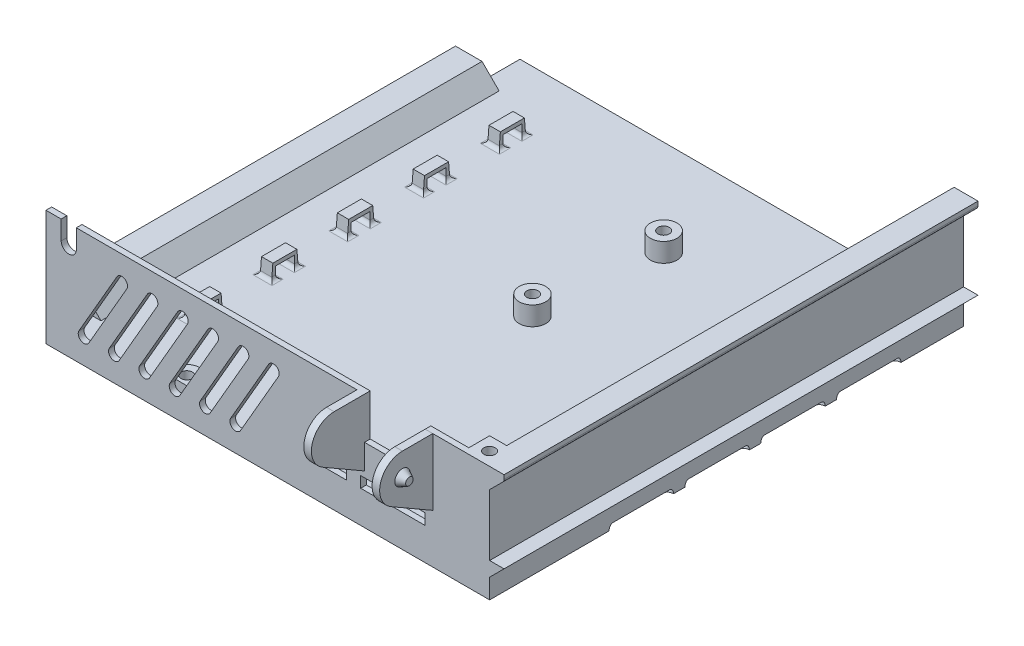
SolidWorks part; units mm, degrees
material "ABS"
ref_plane "Front Plane" through (0, 0, 0) normal (0, 0, 1) x (1, 0, 0)
ref_plane "Top Plane" through (0, 0, 0) normal (0, 1, 0) x (1, 0, 0)
ref_plane "Right Plane" through (0, 0, 0) normal (1, 0, 0) x (0, 0, -1)
ref_axis "Axis1" through (0, 0, 22) along (0, 0, -1)
sketch "Sketch1" plane through (0, 0, 0) normal (0, 1, 0) x (1, 0, 0)
  line L0 (-124, 0) -> (0, 0) construction
  line L1 (124, 0) -> (124, 125) construction
  line L2 (124, 125) -> (-124, 125) construction
  line L3 (-124, 125) -> (-124, 0) construction
  line L4 (40.25, 3.85) -> (40.25, 1.6) construction
  line L5 (38, 101.6) -> (108, 101.6)
  line L6 (38, 101.6) -> (38, 1.6)
  line L7 (38, 1.6) -> (108, 1.6)
  line L8 (108, 101.6) -> (108, 1.6)
  line L9 (38, 101.6) -> (108, 1.6) construction
  line L10 (38, 1.6) -> (108, 101.6) construction
  line L11 (40.25, 3.85) -> (38, 3.85) construction
  line L12 (-113.29, 77.51) -> (-115.54, 77.51) construction
  line L13 (77.2, 11.6) -> (86.2, 11.6)
  line L14 (77.2, 11.6) -> (77.2, 1.6)
  line L15 (77.2, 1.6) -> (86.2, 1.6)
  line L16 (86.2, 11.6) -> (86.2, 1.6)
  line L17 (77.2, 11.6) -> (86.2, 1.6) construction
  line L18 (77.2, 1.6) -> (86.2, 11.6) construction
  line L19 (90, 16.6) -> (107, 16.6)
  line L20 (90, 16.6) -> (90, 1.6)
  line L21 (90, 1.6) -> (107, 1.6)
  line L22 (107, 16.6) -> (107, 1.6)
  line L23 (90, 16.6) -> (107, 1.6) construction
  line L24 (90, 1.6) -> (107, 16.6) construction
  line L25 (-115.54, 113.59) -> (-92.46, 113.59)
  line L26 (-115.54, 113.59) -> (-115.54, 71.41)
  line L27 (-115.54, 71.41) -> (-92.46, 71.41)
  line L28 (-92.46, 113.59) -> (-92.46, 71.41)
  line L29 (-115.54, 113.59) -> (-92.46, 71.41) construction
  line L30 (-115.54, 71.41) -> (-92.46, 113.59) construction
  line L31 (-113.29, 77.51) -> (-113.29, 71.41) construction
  line L32 (-94.71, 107.49) -> (-94.71, 113.59) construction
  line L33 (-94.71, 107.49) -> (-92.46, 107.49) construction
  line L34 (-64.5, 85.45) -> (-68, 85.45) construction
  line L35 (-65, 88.95) -> (-15, 88.95)
  line L36 (-68, 85.95) -> (-68, 6.95)
  line L37 (-65, 3.95) -> (-15, 3.95)
  line L38 (-12, 85.95) -> (-12, 6.95)
  line L39 (-68, 88.95) -> (-12, 3.95) construction
  line L40 (-68, 3.95) -> (-12, 88.95) construction
  line L41 (-64.5, 85.45) -> (-15.5, 85.45) construction
  line L42 (-64.5, 85.45) -> (-64.5, 27.45) construction
  line L43 (-64.5, 27.45) -> (-15.5, 27.45) construction
  line L44 (-15.5, 85.45) -> (-15.5, 27.45) construction
  line L45 (0, 0) -> (0, 125) construction
  line L46 (0, 0) -> (124, 0) construction
  line L47 (-64.5, 85.45) -> (-64.5, 88.95) construction
  line L48 (73, 0.1) -> (73, 125) construction
  line L49 (-65.69, 22.9) -> (-49.81, 22.9)
  line L50 (-65.69, 22.9) -> (-65.69, 1.5)
  line L51 (-65.69, 1.5) -> (-49.81, 1.5)
  line L52 (-49.81, 22.9) -> (-49.81, 1.5)
  line L53 (-65.69, 22.9) -> (-49.81, 1.5) construction
  line L54 (-65.69, 1.5) -> (-49.81, 22.9) construction
  line L55 (-45.65, 19.42) -> (-32.35, 19.42)
  line L56 (-45.65, 19.42) -> (-45.65, 1.5)
  line L57 (-45.65, 1.5) -> (-32.35, 1.5)
  line L58 (-32.35, 19.42) -> (-32.35, 1.5)
  line L59 (-45.65, 19.42) -> (-32.35, 1.5) construction
  line L60 (-45.65, 1.5) -> (-32.35, 19.42) construction
  line L61 (-27.65, 19.42) -> (-14.35, 19.42)
  line L62 (-27.65, 19.42) -> (-27.65, 1.5)
  line L63 (-27.65, 1.5) -> (-14.35, 1.5)
  line L64 (-14.35, 19.42) -> (-14.35, 1.5)
  line L65 (-27.65, 19.42) -> (-14.35, 1.5) construction
  line L66 (-27.65, 1.5) -> (-14.35, 19.42) construction
  line L67 (-40, 0) -> (-40, 125) construction
  line L68 (-113.29, 11.41) -> (-113.29, 17.51) construction
  line L69 (-115.54, 53.59) -> (-92.46, 53.59)
  line L70 (-115.54, 53.59) -> (-115.54, 11.41)
  line L71 (-115.54, 11.41) -> (-92.46, 11.41)
  line L72 (-92.46, 53.59) -> (-92.46, 11.41)
  line L73 (-115.54, 53.59) -> (-92.46, 11.41) construction
  line L74 (-115.54, 11.41) -> (-92.46, 53.59) construction
  line L75 (-113.29, 17.51) -> (-115.54, 17.51) construction
  line L76 (-94.71, 53.59) -> (-94.71, 47.49) construction
  line L77 (-94.71, 47.49) -> (-92.46, 47.49) construction
  line L78 (-104, 0) -> (-104, 32.5) construction
  line L79 (-104, 32.5) -> (-104, 92.5) construction
  line L80 (-104, 92.5) -> (-104, 125) construction
  line L81 (-64.5, 27.45) -> (-15.5, 85.45) construction
  line L82 (-15.5, 27.45) -> (-64.5, 85.45) construction
  circle A0 centre (105, 81.6) radius 1.75
  circle A1 centre (105, 19.6) radius 1.75
  circle A2 centre (70.1, 99.8) radius 1.75
  circle A3 centre (67.3, 68) radius 1.75
  circle A4 centre (40.25, 3.85) radius 1.75
  circle A5 centre (-94.71, 107.49) radius 1.4
  circle A6 centre (-113.29, 77.51) radius 1.4
  arc A7 (-15, 3.95) -> (-12, 6.95) centre (-15, 6.95) ccw
  arc A8 (-68, 6.95) -> (-65, 3.95) centre (-65, 6.95) ccw
  arc A9 (-15, 88.95) -> (-12, 85.95) centre (-15, 85.95) cw
  arc A10 (-65, 88.95) -> (-68, 85.95) centre (-65, 85.95) ccw
  circle A11 centre (-64.5, 85.45) radius 1.375
  circle A12 centre (-15.5, 85.45) radius 1.375
  circle A13 centre (-64.5, 27.45) radius 1.375
  circle A14 centre (-15.5, 27.45) radius 1.375
  circle A15 centre (-94.71, 47.49) radius 1.4
  circle A16 centre (-113.29, 17.51) radius 1.4
  circle A17 centre (40.25, 3.85) radius 2.84
  point P0 (73, 51.6)
  point P3 (-104, 92.5)
  point P4 (0, 0)
  point P24 (81.7, 6.6)
  point P30 (98.5, 9.1)
  point P47 (-40, 46.45)
  point P65 (-39, 10.46)
  point P69 (-57.75, 12.2)
  point P84 (-21, 10.46)
  point P89 (-104, 32.5)
  point P111 (-40, 56.45)
  dimension "D5" = 3.5
  dimension "D26" = 3
  dimension "D27" = 2.75
  dimension "D44" = 2.8
  dimension "D49" = 5.68
  dimension "D1" = 248
  dimension "D2" = 125
  dimension "D3" = 100
  dimension "D4" = 70
  dimension "D6" = 20
  dimension "D7" = 3
  dimension "D8" = 82
  dimension "D9" = 1.8
  dimension "D10" = 37.9
  dimension "D11" = 33.6
  dimension "D12" = 40.7
  dimension "D13" = 2.25
  dimension "D14" = 9
  dimension "D15" = 10
  dimension "D16" = 26.3
  dimension "D17" = 17
  dimension "D18" = 15
  dimension "D19" = 9.5
  dimension "D20" = 23.08
  dimension "D21" = 42.18
  dimension "D22" = 6.1
  dimension "D23" = 2.25
  dimension "D24" = 85
  dimension "D25" = 56
  dimension "D28" = 58
  dimension "D29" = 49
  dimension "D30" = 10.25
  dimension "D31" = 29
  dimension "D32" = 47
  dimension "D33" = 21.4
  dimension "D34" = 15.88
  dimension "D35" = 2.45
  dimension "D36" = 13.3
  dimension "D37" = 17.92
  dimension "D38" = 2.45
  dimension "D39" = 2.45
  dimension "D40" = 2.25
  dimension "D41" = 1.6
  dimension "D42" = 40
  dimension "D43" = 1.5
  dimension "D45" = 60
  dimension "D46" = 3.5
  dimension "D47" = 20
  dimension "D48" = 16
sketch "Sketch2" plane through (0, 0, 0) normal (0, 1, 0) x (1, 0, 0)
  line L0 (124, 125) -> (-124, 125) construction
  line L1 (124, 0) -> (7, 0)
  line L2 (124, 0) -> (124, 125)
  line L3 (124, 125) -> (7, 125)
  line L4 (7, 0) -> (7, 125)
  line L5 (124, 0) -> (7, 125) construction
  line L6 (124, 125) -> (7, 0) construction
  point P4 (65.5, 62.5)
  dimension "D1" = 7
extrude "Boss-Extrude1" add sketch "Sketch2" along normal blind 2.5
sketch "Sketch3" plane through (0, 2.5, 0) normal (0, 1, 0) x (1, 0, 0)
  circle A0 centre (105, 19.6) radius 1.5
  circle A1 centre (67.3, 68) radius 1.5
  circle A2 centre (105, 81.6) radius 1.5
  circle A3 centre (70.1, 99.8) radius 1.5
  circle A4 centre (40.25, 3.85) radius 1.5
  circle A5 centre (40.25, 3.85) radius 3.5
  circle A6 centre (105, 19.6) radius 3.5
  circle A7 centre (67.3, 68) radius 3.5
  circle A8 centre (105, 81.6) radius 3.5
  circle A9 centre (70.1, 99.8) radius 3.5
  dimension "D1" = 3
  dimension "D2" = 2
extrude "Boss-Extrude2" add sketch "Sketch3" along normal blind 5
sketch "Sketch5" plane through (0, 2.5, 0) normal (0, 1, 0) x (1, 0, 0)
  line L0 (124, 0) -> (124, 125) construction
  line L1 (7, 0) -> (124, 0)
  line L2 (7, 0) -> (7, 1.5)
  line L3 (7, 1.5) -> (124, 1.5)
  line L4 (124, 0) -> (124, 1.5)
  line L5 (7, 0) -> (124, 1.5) construction
  line L6 (7, 1.5) -> (124, 0) construction
  point P4 (65.5, 0.75)
  dimension "D1" = 1.5
extrude "Boss-Extrude3" add sketch "Sketch5" along normal blind 28
sketch "Sketch6" plane through (0, 0, 0) normal (0, 0, 1) x (1, 0, 0)
  line L0 (77.2, 0) -> (86.2, 0) construction
  line L1 (77.2, 0) -> (86.2, 0) construction
  line L2 (90, 0) -> (107, 0) construction
  line L3 (90, 0) -> (107, 0) construction
  line L4 (77.2, 0) -> (77.2, 2.5) construction
  line L5 (77.2, 2.5) -> (77.2, 7.5) construction
  line L6 (77.2, 7.5) -> (77.2, 8.5) construction
  line L7 (77.2, 8.5) -> (86.2, 8.5)
  line L8 (86.2, 8.5) -> (86.2, 13.6)
  line L9 (86.2, 13.6) -> (77.2, 13.6)
  line L10 (77.2, 13.6) -> (77.2, 8.5)
  line L11 (90, 8.5) -> (107, 8.5)
  line L12 (107, 8.5) -> (107, 11.4)
  line L13 (107, 11.4) -> (90, 11.4)
  line L14 (90, 11.4) -> (90, 8.5)
  line L15 (77.2, 8.5) -> (86.2, 13.6) construction
  line L16 (77.2, 13.6) -> (86.2, 8.5) construction
  line L18 (75.95, 15.8) -> (87.45, 15.8) construction
  line L19 (75.95, 15.8) -> (75.95, 6.3) construction
  line L20 (75.95, 6.3) -> (87.45, 6.3) construction
  line L21 (87.45, 15.8) -> (87.45, 6.3) construction
  line L22 (75.95, 15.8) -> (87.45, 6.3) construction
  line L23 (75.95, 6.3) -> (87.45, 15.8) construction
  point P9 (81.7, 11.05)
  dimension "D1" = 2.5
  dimension "D2" = 5
  dimension "D3" = 1
  dimension "D4" = 9
  dimension "D5" = 17
  dimension "D6" = 2.9
  dimension "D7" = 5.1
  dimension "D8" = 11.5
  dimension "D9" = 9.5
extrude "Cut-Extrude1" cut sketch "Sketch6" against normal up to surface (1.5 mm away) up to face at (52.875, 10.75, -1.5)
sketch "Sketch7" plane through (0, 0, 0) normal (0, 0, 1) x (1, 0, 0)
  line L0 (124, 0) -> (124, 5.2)
  line L1 (124, 30.5) -> (124, 0) construction
  line L2 (124, 5.2) -> (125.8, 7)
  line L3 (125.8, 7) -> (125.8, 0) construction
  line L4 (125.8, 0) -> (124, 0) construction
  line L5 (125.8, 7) -> (121.5, 7)
  line L6 (121.5, 7) -> (121.5, 0)
  line L7 (7, 0) -> (124, 0) construction
  line L8 (121.5, 0) -> (124, 0)
  line L9 (124, 7) -> (124, 25.2)
  line L10 (125.8, 7) -> (125.8, 27) construction
  line L11 (124, 25.2) -> (125.8, 27)
  line L12 (125.8, 0) -> (127.8, 0) construction
  line L13 (127.8, 0) -> (127.8, 29) construction
  line L14 (125.8, 7) -> (127.8, 9)
  line L15 (125.8, 27) -> (127.8, 29)
  line L16 (121.5, 7) -> (121.5, 30.5)
  line L17 (7, 30.5) -> (124, 30.5) construction
  line L18 (121.5, 30.5) -> (127.8, 30.5)
  line L19 (127.8, 30.5) -> (127.8, 29)
  line L20 (127.8, 9) -> (121.5, 9)
  line M19 (7, 0) -> (124, 0)
  line M20 (124, 0) -> (124, 30.5)
  line M21 (124, 30.5) -> (7, 30.5)
  dimension "D1" = 5.2
  dimension "D2" = 7
  dimension "D3" = 1.8
  dimension "D4" = 2.5
  dimension "D5" = 25.2
  dimension "D6" = 27
  dimension "D7" = 2
extrude "Boss-Extrude4" add sketch "Sketch7" against normal up to surface (125 mm away) contours L5 L6 M19 M20 | L2 L5 M20 | L14 L20 L5 M20 | L20 L16 L5 M20 | L20 L9 L16 M20 M21 | L19 L18 L11 L15 M20 region at (122.75, 3.5, 0) region at (124.6, 6.4, 0) region at (125.4595, 8.119, 0) region at (122.75, 8, 0) region at (122.75, 19.75, 0) region at (125.5461, 28.623, 0) up to face at (65.5, 1.25, -125)
fillet "Fillet1" radius 1 1 edges at (127.8, 29, -62.5)
sketch "Sketch9" plane through (0, 0, 0) normal (0, 0, 1) x (1, 0, 0)
  line L0 (7, 7) -> (11.5, 2.5)
  line L1 (7, 0) -> (0, 0)
  line L2 (7, 0) -> (7, 7)
  line L3 (7, 7) -> (0, 7)
  line L4 (0, 0) -> (0, 7)
  line L5 (7, 0) -> (0, 7) construction
  line L6 (7, 7) -> (0, 0) construction
  line L7 (11.5, 2.5) -> (7, 2.5)
  line L8 (7, 0) -> (124, 0) construction
  circle A0 centre (3.5, 3.5) radius 1.5
  point P4 (3.5, 3.5)
  line M15 (7, 30.5) -> (7, 0)
  dimension "D2" = 3
  dimension "D1" = 7
  dimension "D3" = 2.5
  dimension "D4" = 45
extrude "Boss-Extrude5" add sketch "Sketch9" against normal offset from surface (105 mm away) 10 from offset 10 contours L4 L1 L2 L3 A0 M15 | L7 L0 M15 region at (8.5, 4, 0) region at (6.901, 4.75, 0) up to face at (105.3315, 14.3743, -125) offset against normal yes
sketch "Sketch12" plane through (0, 30.5, 0) normal (0, 1, 0) x (1, 0, 0)
  line L1 (124, 0) -> (117, 0)
  line L2 (124, 0) -> (124, 7)
  line L3 (124, 7) -> (117, 7)
  line L4 (117, 0) -> (117, 7)
  line L5 (124, 0) -> (117, 7) construction
  line L6 (124, 7) -> (117, 0) construction
  circle A0 centre (120.5, 3.5) radius 1.5 construction
  point P4 (120.5, 3.5)
  dimension "D2" = 3
  dimension "D1" = 7
extrude "Boss-Extrude7" add sketch "Sketch12" against normal up to surface (28 mm away) up to face at (37.45, 2.5, -51.185)
sketch "Sketch13" plane through (0, 30.5, 0) normal (0, 1, 0) x (1, 0, 0)
  circle A0 centre (120.5, 3.5) radius 1.5 construction
  circle A1 centre (120.5, 3.5) radius 1.5
extrude "Cut-Extrude3" cut sketch "Sketch13" against normal blind 10
sketch "Sketch15" plane through (0, 0, 0) normal (-1, 0, 0) x (0, 0, 1)
  line L0 (-125, 2.5) -> (-1.5, 2.5) construction
  line L1 (-107.5, 2.5) -> (-108.5, 2.5)
  line L2 (-107.5, 2.5) -> (-102.5, 2.5) construction
  line L3 (-107.5, 2.5) -> (-107.5, 5.5)
  line L4 (-107.5, 5.5) -> (-102.5, 5.5)
  line L5 (-102.5, 2.5) -> (-102.5, 5.5)
  line L6 (-107.5, 2.5) -> (-102.5, 5.5) construction
  line L7 (-107.5, 5.5) -> (-102.5, 2.5) construction
  line L8 (-108.5, 2.5) -> (-108.1701, 6.5)
  line L9 (-108.1701, 6.5) -> (-101.8299, 6.5)
  line L10 (-101.8299, 6.5) -> (-101.5, 2.5)
  line L11 (-101.5, 2.5) -> (-102.5, 2.5)
  line L12 (-115, 7) -> (-115, 0) construction
  point P8 (-105, 4)
  dimension "D1" = 3
  dimension "D2" = 5
  dimension "D3" = 1
  dimension "D4" = 1
  dimension "D5" = 0.75
  dimension "D6" = 10
extrude "Boss-Extrude8" add sketch "Sketch15" along normal blind 3 from offset 25 offset against normal yes
pattern_linear "LPattern1" count 5 spacing 20 along (0, 0, 1) of "Boss-Extrude8"
fillet "Fillet2" radius 1 40 edges at (25, 2.5, -62) (23.5, 2.5, -62.5) (23.5, 2.5, -61.5) (22, 2.5, -62) (25, 2.5, -68) (22, 2.5, -68) (23.5, 2.5, -67.5) (23.5, 2.5, -68.5) (25, 2.5, -82) (23.5, 2.5, -82.5) (23.5, 2.5, -81.5) (22, 2.5, -82) (25, 2.5, -88) (23.5, 2.5, -88.5) (23.5, 2.5, -87.5) (22, 2.5, -88) (25, 2.5, -102) (23.5, 2.5, -102.5) (23.5, 2.5, -101.5) (22, 2.5, -102) (25, 2.5, -108) (23.5, 2.5, -108.5) (23.5, 2.5, -107.5) (22, 2.5, -108) (25, 2.5, -22) (23.5, 2.5, -22.5) (23.5, 2.5, -21.5) (22, 2.5, -22) (25, 2.5, -28) (23.5, 2.5, -28.5) (23.5, 2.5, -27.5) (22, 2.5, -28) (25, 2.5, -42) (23.5, 2.5, -42.5) (23.5, 2.5, -41.5) (22, 2.5, -42) (25, 2.5, -48) (23.5, 2.5, -48.5) (23.5, 2.5, -47.5) (22, 2.5, -48)
sketch "Sketch16" plane through (0, 0, 0) normal (0, 0, 1) x (1, 0, 0)
  line L0 (27, 23.9103) -> (17, 6.5897) construction
  line L1 (28.299, 23.1603) -> (18.299, 5.8397)
  line L2 (25.701, 24.6603) -> (15.701, 7.3397)
  line L3 (17, 6.5897) -> (27, 6.5897) construction
  line L4 (27, 6.5897) -> (27, 23.9103) construction
  line L5 (7, 15.25) -> (124, 15.25) construction
  line L6 (7, 30.5) -> (7, 0) construction
  line L7 (124, 25.2) -> (124, 9) construction
  arc A0 (28.299, 23.1603) -> (25.701, 24.6603) centre (27, 23.9103) ccw
  arc A1 (15.701, 7.3397) -> (18.299, 5.8397) centre (17, 6.5897) ccw
  point P2 (22, 15.25)
  dimension "D3" = 1.5
  dimension "D1" = 60
  dimension "D2" = 20
  dimension "D4" = 15
extrude "Cut-Extrude4" cut sketch "Sketch16" against normal up to surface (1.5 mm away) up to face at (81.7, 11.05, -1.5)
pattern_linear "LPattern2" count 6 spacing 8 along (1, 0, 0) of "Cut-Extrude4"
ref_plane "Plane2" through (59.5, -59.5, 0) normal (-0.7071, 0.7071, 0) x (0, 0, 1)
sketch "Sketch18" plane through (59.5, -59.5, 0) normal (-0.7071, 0.7071, 0) x (0, 0, 1)
  line L0 (-107.5, 87.6812) -> (-92.5, 87.6812) construction
  line L1 (-125, 87.6812) -> (-7, 87.6812) construction
  line L2 (-107.5, 88.6812) -> (-92.5, 88.6812)
  line L3 (-107.5, 86.6812) -> (-92.5, 86.6812)
  arc A0 (-107.5, 88.6812) -> (-107.5, 86.6812) centre (-107.5, 87.6812) ccw
  arc A1 (-92.5, 86.6812) -> (-92.5, 88.6812) centre (-92.5, 87.6812) ccw
  point P4 (-100, 87.6812)
  dimension "D1" = 15
  dimension "D2" = 1
  dimension "D3" = 25
extrude "Cut-Extrude5" cut sketch "Sketch18" against normal through all both and the other way through all
pattern_linear "LPattern3" count 4 spacing 20 along (0, 0, 1) of "Cut-Extrude5"
ref_plane "Plane3" through (99, 0, 0) normal (1, 0, 0) x (0, 0, -1)
ref_plane "Plane4" through (109, 0, 0) normal (1, 0, 0) x (0, 0, -1)
sketch "Sketch20" plane through (109, 0, 0) normal (1, 0, 0) x (0, 0, -1)
  line L0 (0, 25.2) -> (0, 9) construction
  line L1 (125, 30.5) -> (0, 30.5) construction
  line L2 (-8, 30.5) -> (0, 30.5)
  line L3 (-11, 19.3038) -> (0, 12.953)
  line L4 (0, 30.5) -> (0, 12.953)
  arc A0 (-8, 30.5) -> (-11, 19.3038) centre (-8, 24.5) ccw
  dimension "D1" = 12
  dimension "D3" = 60
  dimension "D2" = 8
extrude "Boss-Extrude9" add sketch "Sketch20" against normal blind 2 separate body
ref_plane "Plane5" through (0, 0, 8) normal (0, 0, 1) x (1, 0, 0)
sketch "Sketch24" plane through (0, 0, 8) normal (0, 0, 1) x (1, 0, 0)
  line L0 (109, 24.5) -> (110.84, 24.5)
  line L1 (110.84, 24.5) -> (110.84, 25.5)
  line L2 (110.84, 25.5) -> (109, 26.5)
  line L3 (109, 26.5) -> (109, 24.5)
  dimension "D1" = 1.84
  dimension "D2" = 2
  dimension "D3" = 1
revolve "Revolve1" add sketch "Sketch24" angle 360 about L0
mirror "Mirror2" about plane through (99, 0, 0) normal (1, 0, 0) of "Revolve1", "Boss-Extrude9"
sketch "Sketch25" plane through (0, 0, 0) normal (0, 0, 1) x (1, 0, 0)
  line L0 (107, 30.5) -> (107, 19.3038) construction
  line L1 (91, 30.5) -> (107, 30.5)
  line L2 (91, 30.5) -> (91, 19.5)
  line L3 (91, 19.5) -> (107, 19.5)
  line L4 (107, 30.5) -> (107, 19.5)
  line L5 (91, 30.5) -> (107, 19.5) construction
  line L6 (91, 19.5) -> (107, 30.5) construction
  point P4 (99, 25)
  dimension "D1" = 11
extrude "Cut-Extrude6" cut sketch "Sketch25" against normal up to surface (1.5 mm away) up to face at (38, 15.25, -1.5)
sketch "Sketch26" plane through (0, 0, 0) normal (0, 0, 1) x (1, 0, 0)
  line L0 (13, 30.5) -> (13, 25.5) construction
  line L1 (7, 30.5) -> (89, 30.5) construction
  line L2 (15, 30.5) -> (15, 25.5)
  line L3 (11, 30.5) -> (11, 25.5)
  line L4 (7, 30.5) -> (7, 0) construction
  line L5 (11, 30.5) -> (15, 30.5)
  arc A0 (15, 30.5) -> (11, 30.5) centre (13, 30.5) ccw
  arc A1 (11, 25.5) -> (15, 25.5) centre (13, 25.5) ccw
  point P4 (13, 28)
  line M41 (89, 30.5) -> (7, 30.5)
  dimension "D1" = 5
  dimension "D2" = 2
  dimension "D3" = 6
extrude "Cut-Extrude7" cut sketch "Sketch26" against normal up to surface (1.5 mm away) contours L3 A1 L2 L5 M41 region at (13, 27.1994, 0) up to face at (63.1696, 16.1268, -1.5)
equation "\"D16@Sketch1\"=22.8+3.5"
equation "\"D19@Sketch1\"=6+3.5"
equation "\"D1@Boss-Extrude3\"=33-2.5-2.5"
